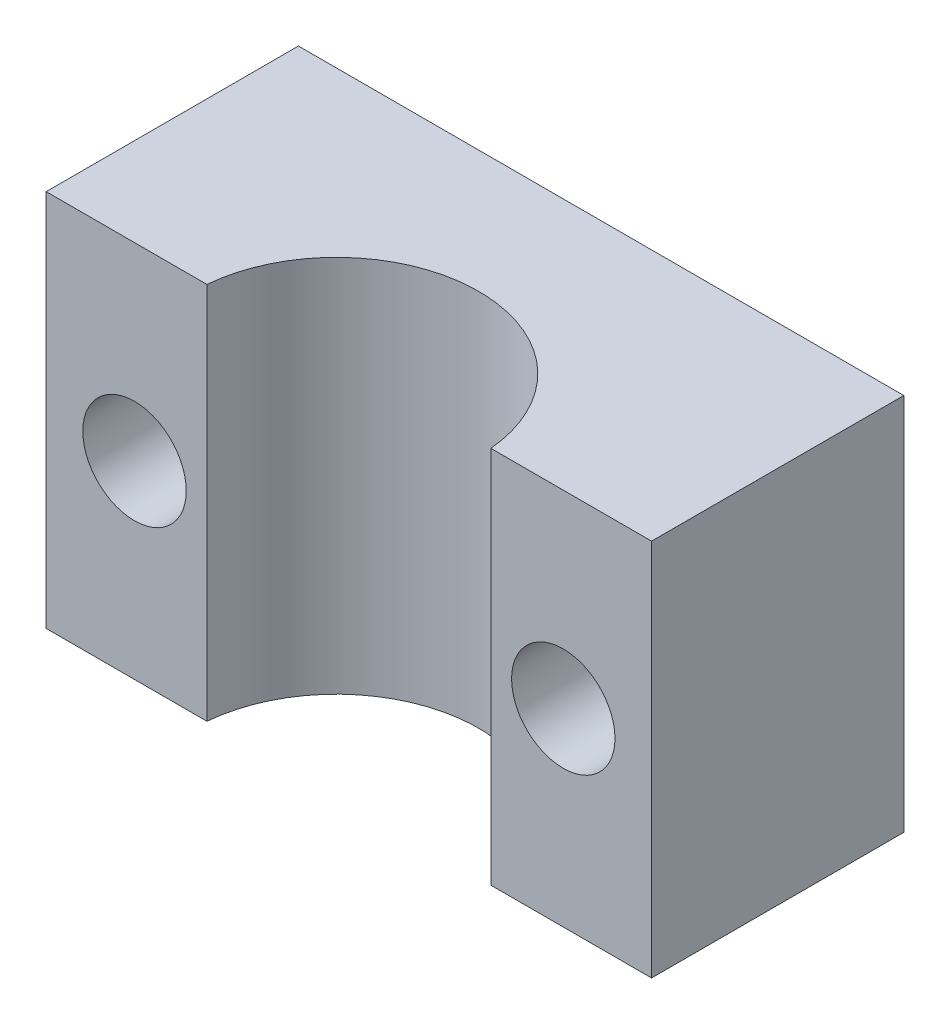
SolidWorks part; units mm, degrees
ref_plane "Спереди" through (0, 0, 0) normal (0, 0, 1) x (1, 0, 0)
ref_plane "Сверху" through (0, 0, 0) normal (0, 1, 0) x (1, 0, 0)
ref_plane "Справа" through (0, 0, 0) normal (1, 0, 0) x (0, 0, -1)
sketch "Эскиз1" plane through (0, 0, 0) normal (0, 1, 0) x (1, 0, 0)
  line L1 (-24, -10) -> (24, -10)
  line L2 (-24, -10) -> (-24, 10)
  line L3 (-24, 10) -> (24, 10)
  line L4 (24, -10) -> (24, 10)
  line L5 (-24, -10) -> (24, 10) construction
  line L6 (-24, 10) -> (24, -10) construction
  point P0 (0, 0)
  dimension "D1" = 48
  dimension "D2" = 20
extrude "Бобышка-Вытянуть1" add sketch "Эскиз1" along normal blind 30
sketch "Эскиз2" plane through (0, 0, 10) normal (0, 0, 1) x (1, 0, 0)
  line L0 (-7, 30) -> (-7, 0)
  line L1 (-24, 30) -> (24, 30) construction
  line L2 (-24, 0) -> (24, 0) construction
  line L3 (-7, 0) -> (7, 0)
  line L4 (7, 0) -> (7, 30)
  line L5 (7, 30) -> (-7, 30)
  dimension "D1" = 17
  dimension "D2" = 14
extrude "Вырез-Вытянуть1" cut sketch "Эскиз2" against normal blind 7
sketch "Эскиз7" plane through (24, 0, 0) normal (1, 0, 0) x (0, 0, -1)
  line L1 (32, 30) -> (32, 0)
  line L2 (32, 0) -> (10, 0)
  line L3 (-10, 0) -> (10, 0)
  line L4 (10, 0) -> (10.066, 0.2736)
  line L5 (10, 30) -> (32, 30)
  line L8 (10, 0) -> (10, 30)
  line M4 (10, 0) -> (10, 30)
  dimension "D3" = 22
extrude "Бобышка-Вытянуть2" add sketch "Эскиз7" against normal blind 48 contours L5 M4 region at (24, 15, -21)
sketch "Эскиз8" plane through (24, 0, 0) normal (1, 0, 0) x (0, 0, -1)
  line L0 (11, 0) -> (11, 30)
  line L1 (-10, 30) -> (32, 30) construction
  line L2 (11, 30) -> (32, 30)
  line L3 (11, 0) -> (32, 0)
  line L4 (32, 0) -> (32, 30)
  line L5 (-10, 0) -> (32, 0) construction
  point P16 (11, 0)
extrude "Вырез-Вытянуть2" cut sketch "Эскиз8" against normal blind 14
sketch "Эскиз9" plane through (-24, 0, 0) normal (-1, 0, 0) x (0, 0, 1)
  line L0 (-11, 0) -> (-11, 30)
  line L1 (-32, 30) -> (10, 30) construction
  line L2 (-11, 30) -> (-32, 30)
  line L3 (-32, 0) -> (10, 0) construction
  line L4 (-11, 0) -> (-32, 0)
  line L5 (-32, 0) -> (-32, 30)
  point P15 (-11, 0)
extrude "Вырез-Вытянуть3" cut sketch "Эскиз9" against normal blind 14
sketch "Эскиз11" plane through (-10, 0, 0) normal (-1, 0, 0) x (0, 0, 1)
  line L0 (-32, 30) -> (-11, 0) construction
  line L2 (-32, 0) -> (-11, 0) construction
  line L3 (-16.4, 4.9) -> (-16.4, 25.1)
  line L6 (-16.4, 4.9) -> (-26.6, 4.9)
  line L7 (-16.4, 25.1) -> (-26.6, 25.1)
  line L8 (-26.6, 4.9) -> (-26.6, 25.1)
  line L9 (-16.4, 4.9) -> (-26.6, 25.1) construction
  line L10 (-16.4, 25.1) -> (-26.6, 4.9) construction
  point P7 (-21.5, 15)
  point P8 (-21.5, 15)
  dimension "D1" = 20.2
  dimension "D2" = 10.2
extrude "Вырез-Вытянуть4" cut sketch "Эскиз11" against normal through all
sketch "Эскиз13" plane through (0, 0, -11) normal (0, 0, -1) x (-1, 0, 0)
  line L0 (24, 15) -> (10, 15) construction
  line L1 (24, 0) -> (24, 30) construction
  line L2 (10, 0) -> (10, 30) construction
  line L3 (-10, 15) -> (-24, 15) construction
  line L4 (-10, 30) -> (-10, 0) construction
  line L5 (-24, 30) -> (-24, 0) construction
  circle A0 centre (17, 15) radius 4.1
  circle A1 centre (-17, 15) radius 4.1
  dimension "D1" = 8.2
extrude "Вырез-Вытянуть5" cut sketch "Эскиз13" against normal through all
fillet "Скругление1" radius 7 2 edges at (-7, 15, 3) (7, 15, 3)
sketch "Sketch1" plane through (10, 0, 0) normal (1, 0, 0) x (0, 0, -1)
  line L0 (16.4, 25.1) -> (26.6, 4.9) construction
  line L2 (26.6, 4.9) -> (16.4, 4.9)
  line L3 (26.6, 4.9) -> (26.6, 25.1)
  line L4 (26.6, 25.1) -> (16.4, 25.1)
  line L5 (16.4, 4.9) -> (16.4, 25.1)
  line L6 (26.6, 4.9) -> (16.4, 25.1) construction
  line L7 (26.6, 25.1) -> (16.4, 4.9) construction
  point P4 (21.5, 15)
extrude "Boss-Extrude1" add sketch "Sketch1" against normal blind 4
sketch "Sketch2" plane through (0, 30, 0) normal (0, 1, 0) x (1, 0, 0)
  line L0 (-10, 11) -> (10, 32) construction
  line L2 (-10, 32) -> (10, 32)
  line L3 (-10, 32) -> (-10, 11)
  line L4 (-10, 11) -> (10, 11)
  line L5 (10, 32) -> (10, 11)
  line L6 (-10, 32) -> (10, 11) construction
  line L7 (-10, 11) -> (10, 32) construction
  point P4 (0, 21.5)
extrude "Cut-Extrude1" cut sketch "Sketch2" against normal through all
sketch "Sketch3" plane through (0, 30, 0) normal (0, 1, 0) x (1, 0, 0)
  line L0 (7, -10) -> (-7, -10) construction
  circle A0 centre (0, -10) radius 11.3
  dimension "D1" = 22.6
extrude "Cut-Extrude2" cut sketch "Sketch3" against normal through all
sketch "Sketch4" plane through (0, 0, 10) normal (0, 0, 1) x (1, 0, 0)
  line L0 (-24, 15) -> (24, 15) construction
  line L1 (-24, 30) -> (-24, 0) construction
  line L2 (24, 30) -> (24, 0) construction
  line L4 (24, 0) -> (-24, 0)
  line L5 (24, 0) -> (24, 30)
  line L6 (24, 30) -> (-24, 30)
  line L7 (-24, 0) -> (-24, 30)
  line L8 (24, 0) -> (-24, 30) construction
  line L9 (24, 30) -> (-24, 0) construction
  point P6 (0, 15)
extrude "Cut-Extrude3" cut sketch "Sketch4" against normal blind 1
